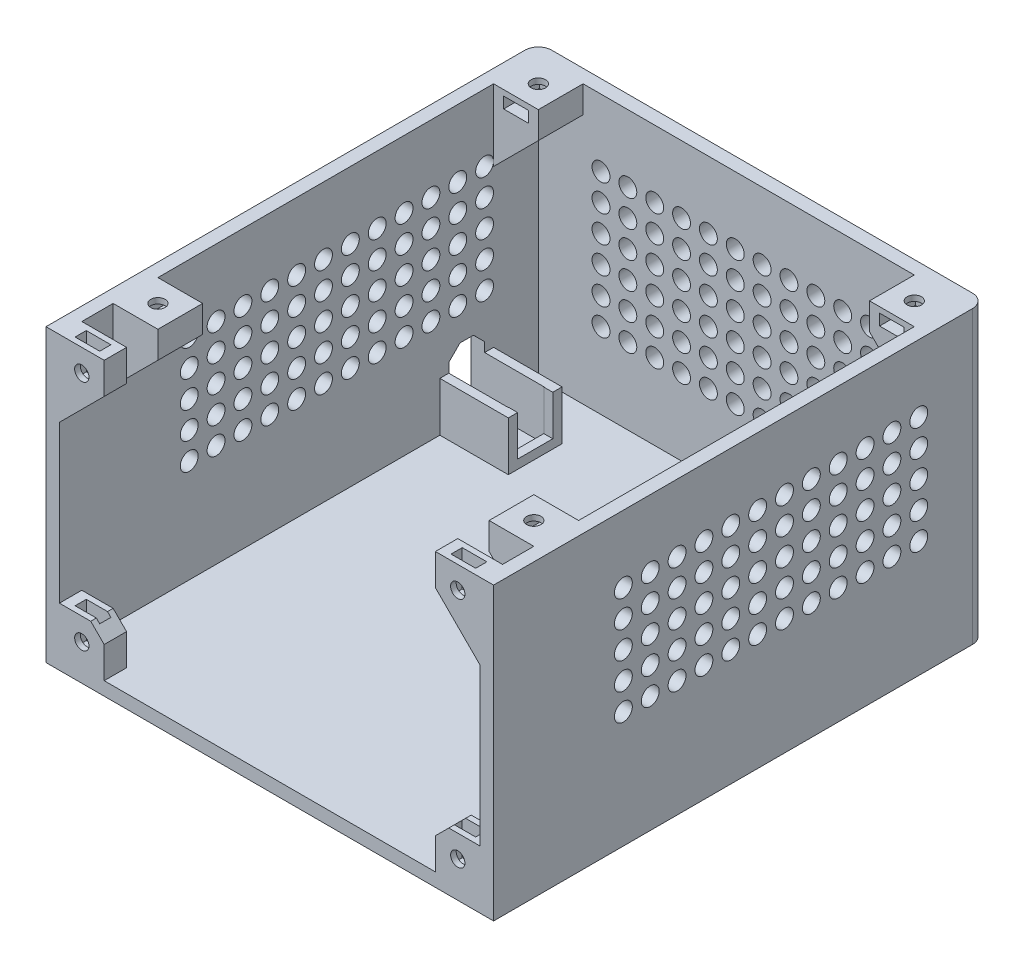
SolidWorks part; units mm, degrees
ref_plane "Спереди" through (0, 0, 0) normal (0, 0, 1) x (1, 0, 0)
ref_plane "Сверху" through (0, 0, 0) normal (0, 1, 0) x (1, 0, 0)
ref_plane "Справа" through (0, 0, 0) normal (1, 0, 0) x (0, 0, -1)
sketch "Эскиз2" plane through (0, 0, 0) normal (0, 0, 1) x (1, 0, 0)
  line L1 (-50, 32.5) -> (50, 32.5)
  line L2 (-50, 32.5) -> (-50, -32.5)
  line L3 (-50, -32.5) -> (50, -32.5)
  line L4 (50, 32.5) -> (50, -32.5)
  line L5 (-50, 32.5) -> (50, -32.5) construction
  line L6 (-50, -32.5) -> (50, 32.5) construction
  point P0 (0, 0)
  dimension "D1" = 65
  dimension "D2" = 100
extrude "Бобышка-Вытянуть1" add sketch "Эскиз2" along normal blind 110
sketch "Эскиз3" plane through (0, 32.5, 0) normal (0, 1, 0) x (1, 0, 0)
  line L0 (-50, -110) -> (-50, 0) construction
  line L1 (-47, -3) -> (47, -3)
  line L2 (-47, -3) -> (-47, -110)
  line L3 (-47, -110) -> (47, -110)
  line L4 (47, -3) -> (47, -110)
  line L5 (-47, -3) -> (47, -110) construction
  line L6 (-47, -110) -> (47, -3) construction
  line L8 (50, 0) -> (-50, 0) construction
  point P0 (0, -56.5)
  dimension "D1" = 107
  dimension "D2" = 94
  dimension "D3" = 3
  dimension "D4" = 3
extrude "Вырез-Вытянуть1" cut sketch "Эскиз3" against normal blind 62
sketch "Эскиз4" plane through (0, 0, 110) normal (0, 0, 1) x (1, 0, 0)
  line L1 (-47, -19.5) -> (-37, -19.5)
  line L2 (-47, -19.5) -> (-47, -29.5)
  line L3 (-47, -29.5) -> (-37, -29.5)
  line L4 (-37, -19.5) -> (-37, -29.5)
  line L5 (-47, -19.5) -> (-37, -29.5) construction
  line L6 (-47, -29.5) -> (-37, -19.5) construction
  line L11 (37, -19.5) -> (47, -19.5)
  line L12 (47, -19.5) -> (47, -29.5)
  line L13 (37, -29.5) -> (47, -29.5)
  line L14 (37, -19.5) -> (37, -29.5)
  circle A0 centre (-42, -24.5) radius 1.6
  circle A2 centre (42, -24.5) radius 1.6
  point P0 (-42, -24.5)
  dimension "D2" = 3.2
  dimension "D1" = 10
  dimension "D3" = 2
extrude "Бобышка-Вытянуть2" add sketch "Эскиз4" against normal blind 5
sketch "Эскиз5" plane through (0, 0, 110) normal (0, 0, 1) x (1, 0, 0)
  line L1 (-47, 32.5) -> (-37, 32.5)
  line L2 (-47, 32.5) -> (-47, 22.5)
  line L3 (-47, 22.5) -> (-37, 22.5)
  line L4 (-37, 32.5) -> (-37, 22.5)
  line L5 (-47, 32.5) -> (-37, 22.5) construction
  line L6 (-47, 22.5) -> (-37, 32.5) construction
  line L10 (37, 32.5) -> (47, 32.5)
  line L12 (37, 32.5) -> (37, 22.5)
  line L13 (37, 22.5) -> (47, 22.5)
  line L14 (47, 32.5) -> (47, 22.5)
  circle A0 centre (-42, 27.5) radius 1.6
  circle A2 centre (42, 27.5) radius 1.6
  point P0 (-42, 27.5)
  dimension "D4" = 3.2
  dimension "D1" = 10
  dimension "D2" = 10
  dimension "D3" = 2
extrude "Бобышка-Вытянуть3" add sketch "Эскиз5" against normal blind 5
sketch "Эскиз6" plane through (0, 32.5, 0) normal (0, 1, 0) x (1, 0, 0)
  line L0 (-37, -105) -> (-37, -110) construction
  line L1 (-44.75, -106.25) -> (-39.25, -106.25)
  line L2 (-44.75, -106.25) -> (-44.75, -108.75)
  line L3 (-44.75, -108.75) -> (-39.25, -108.75)
  line L4 (-39.25, -106.25) -> (-39.25, -108.75)
  line L5 (-44.75, -106.25) -> (-39.25, -108.75) construction
  line L6 (-44.75, -108.75) -> (-39.25, -106.25) construction
  line L11 (39.25, -106.25) -> (39.25, -108.75)
  line L12 (39.25, -106.25) -> (44.75, -106.25)
  line L13 (44.75, -106.25) -> (44.75, -108.75)
  line L14 (39.25, -108.75) -> (44.75, -108.75)
  point P0 (-42, -107.5)
  dimension "D1" = 2.5
  dimension "D2" = 5.5
  dimension "D3" = 5
  dimension "D4" = 2.5
  dimension "D6" = 1.25
  dimension "D7" = 2.25
  dimension "D5" = 2
extrude "Вырез-Вытянуть2" cut sketch "Эскиз6" against normal blind 8
sketch "Эскиз8" plane through (0, -19.5, 0) normal (0, 1, 0) x (1, 0, 0)
  line L1 (-44.75, -106.25) -> (-39.25, -106.25)
  line L2 (-44.75, -106.25) -> (-44.75, -108.75)
  line L3 (-44.75, -108.75) -> (-39.25, -108.75)
  line L4 (-39.25, -106.25) -> (-39.25, -108.75)
  line L5 (-44.75, -106.25) -> (-39.25, -108.75) construction
  line L6 (-44.75, -108.75) -> (-39.25, -106.25) construction
  line L12 (39.25, -106.25) -> (39.25, -108.75)
  line L13 (39.25, -106.25) -> (44.75, -106.25)
  line L14 (39.25, -108.75) -> (44.75, -108.75)
  line L15 (44.75, -106.25) -> (44.75, -108.75)
  point P0 (-42, -107.5)
  dimension "D1" = 2.5
  dimension "D2" = 5.5
  dimension "D3" = 2.5
  dimension "D4" = 5
  dimension "D5" = 2
extrude "Вырез-Вытянуть3" cut sketch "Эскиз8" against normal blind 8
chamfer "Фаска1" distance 3 angle 45 4 edges at (-37, 22.5, 107.5) (-37, -19.5, 107.5) (37, -19.5, 107.5) (37, 22.5, 107.5)
sketch "Эскиз13" plane through (-50, 0, 0) normal (-1, 0, 0) x (0, 0, 1)
  line L0 (15, -29.5) -> (23, -29.5)
  line L1 (23, -29.5) -> (23, -16.4)
  line L2 (23, -16.4) -> (20.5058, -13.9)
  line L3 (20.5058, -13.9) -> (17.4942, -13.9)
  line L4 (17.4942, -13.9) -> (15, -16.4)
  line L5 (15, -16.4) -> (15, -29.5)
  line L6 (0, 32.5) -> (0, -32.5) construction
  line L7 (110, -32.5) -> (0, -32.5) construction
  point P6 (19, -13.9)
  point P7 (19, -29.5)
  dimension "D1" = 8
  dimension "D2" = 15.6
  dimension "D3" = 2.5
  dimension "D4" = 15
  dimension "D5" = 3
extrude "Вырез-Вытянуть5" cut sketch "Эскиз13" against normal up to next
sketch "Эскиз15" plane through (0, -29.5, 0) normal (0, 1, 0) x (1, 0, 0)
  line L0 (-47, -25) -> (-31.7, -25)
  line L1 (-31.7, -25) -> (-31.7, -13)
  line L2 (-31.7, -13) -> (-47, -13)
  line L3 (-47, -13) -> (-47, -15)
  line L4 (-47, -15) -> (-33.7, -15)
  line L5 (-33.7, -15) -> (-33.7, -23)
  line L6 (-33.7, -23) -> (-47, -23)
  line L7 (-47, -25) -> (-47, -23)
  line L9 (-47, -3) -> (-47, -15) construction
  line L11 (47, -3) -> (-47, -3) construction
  dimension "D1" = 8
  dimension "D2" = 2
  dimension "D3" = 2
  dimension "D4" = 2
  dimension "D5" = 15.3
  dimension "D6" = 10
extrude "Бобышка-Вытянуть5" add sketch "Эскиз15" along normal blind 11
sketch "Эскиз16" plane through (0, -18.5, 0) normal (0, 1, 0) x (1, 0, 0)
  line L0 (-31.7, -25) -> (-31.7, -13) construction
  line L2 (-34.6087, -15.0713) -> (-28.7913, -15.0713)
  line L3 (-34.6087, -15.0713) -> (-34.6087, -22.9287)
  line L4 (-34.6087, -22.9287) -> (-28.7913, -22.9287)
  line L5 (-28.7913, -15.0713) -> (-28.7913, -22.9287)
  line L6 (-34.6087, -15.0713) -> (-28.7913, -22.9287) construction
  line L7 (-34.6087, -22.9287) -> (-28.7913, -15.0713) construction
  point P3 (-31.7, -19)
  dimension "D1" = 7.8574
  dimension "D2" = 5.8174
extrude "Вырез-Вытянуть6" cut sketch "Эскиз16" against normal blind 9
sketch "Эскиз31" plane through (0, 0, 3) normal (0, 0, 1) x (1, 0, 0)
  line L0 (47, 32.5) -> (47, 26.5)
  line L1 (-47, 32.5) -> (-37, 32.5)
  line L2 (-47, 32.5) -> (-47, 26.5)
  line L3 (-47, 26.5) -> (-37, 26.5)
  line L4 (-37, 32.5) -> (-37, 26.5)
  line L5 (37, 32.5) -> (47, 32.5)
  line L6 (37, 32.5) -> (37, 26.5)
  line L7 (37, 26.5) -> (47, 26.5)
  dimension "D1" = 10
  dimension "D2" = 6
  dimension "D3" = 2
extrude "Бобышка-Вытянуть10" add sketch "Эскиз31" along normal blind 10 separate body
sketch "Эскиз40" plane through (0, 0, 13) normal (0, 0, 1) x (1, 0, 0)
  line L0 (37, 26.5) -> (47, 26.5)
  line L1 (37, 26.5) -> (47, 26.5) construction
  line L2 (47, 26.5) -> (47, 16.5)
  line L3 (47, 16.5) -> (37, 26.5)
  point P5 (44, 26.5)
  point P7 (44, 26.5)
  dimension "D1" = 10
  dimension "D2" = 10
  dimension "D3" = 14.1421
extrude "Бобышка-Вытянуть14" add sketch "Эскиз40" against normal blind 10
sketch "Эскиз42" plane through (0, 0, 13) normal (0, 0, 1) x (1, 0, 0)
  line L0 (-37, 26.5) -> (-47, 26.5)
  line L1 (-47, 26.5) -> (-47, 16.5)
  line L2 (-47, 16.5) -> (-37, 26.5)
  dimension "D1" = 10
  dimension "D2" = 10
  dimension "D3" = 14.1421
extrude "Бобышка-Вытянуть16" add sketch "Эскиз42" against normal blind 10
sketch "Эскиз32" plane through (0, 32.5, 0) normal (0, 1, 0) x (1, 0, 0)
  circle A0 centre (-42, -8) radius 1.6
  circle A1 centre (42, -8) radius 1.6
  point P3 (0, 0)
  point P11 (0, 0)
  dimension "D1" = 3.2
extrude "Вырез-Вытянуть15" cut sketch "Эскиз32" against normal blind 20
sketch "Эскиз34" plane through (0, 0, 110) normal (0, 0, 1) x (1, 0, 0)
  line L0 (-40, 22.5) -> (-47, 15.5)
  line L1 (-47, -19.5) -> (-47, 22.5) construction
  line L2 (-47, 15.5) -> (-47, 22.5)
  line L3 (-47, 22.5) -> (-40, 22.5)
  line L4 (40, 22.5) -> (47, 22.5)
  line L5 (47, 22.5) -> (47, 15.5)
  line L6 (47, -19.5) -> (47, 22.5) construction
  line L7 (47, 15.5) -> (40, 22.5)
  dimension "D1" = 9.8995
  dimension "D2" = 7
  dimension "D3" = 7
  dimension "D4" = 7
  dimension "D5" = 7
  dimension "D6" = 9.8995
extrude "Бобышка-Вытянуть11" add sketch "Эскиз34" against normal blind 5
fillet "Скругление8" radius 3 1 edges at (-50, 0, 0)
fillet "Скругление9" radius 3 1 edges at (50, 0, 0)
sketch "Эскиз35" plane through (0, 0, 13) normal (0, 0, 1) x (1, 0, 0)
  line L0 (-37, 26.5) -> (-37, 32.5) construction
  line L1 (-44.75, 31.25) -> (-39.25, 31.25)
  line L2 (-44.75, 31.25) -> (-44.75, 28.75)
  line L3 (-44.75, 28.75) -> (-39.25, 28.75)
  line L4 (-39.25, 31.25) -> (-39.25, 28.75)
  line L5 (-44.75, 31.25) -> (-39.25, 28.75) construction
  line L6 (-44.75, 28.75) -> (-39.25, 31.25) construction
  line L7 (-37, 32.5) -> (-47, 32.5) construction
  line L8 (39.25, 31.25) -> (44.75, 31.25)
  line L9 (39.25, 31.25) -> (39.25, 28.75)
  line L10 (39.25, 28.75) -> (44.75, 28.75)
  line L11 (44.75, 31.25) -> (44.75, 28.75)
  point P0 (-42, 30)
  dimension "D1" = 5.5
  dimension "D2" = 2.5
  dimension "D3" = 2.25
  dimension "D4" = 5
  dimension "D5" = 1.25
  dimension "D6" = 2
extrude "Вырез-Вытянуть16" cut sketch "Эскиз35" against normal blind 8
sketch "Эскиз36" plane through (-47, 0, 0) normal (1, 0, 0) x (0, 0, -1)
  line L0 (-98, 32.5) -> (-88, 32.5)
  line L1 (-13, 32.5) -> (-105, 32.5) construction
  line L2 (-88, 32.5) -> (-88, 26.5)
  line L3 (-88, 26.5) -> (-98, 26.5)
  line L4 (-98, 26.5) -> (-98, 32.5)
  line L5 (-105, 32.5) -> (-105, 15.5) construction
  point P5 (-98, 29.5)
  dimension "D1" = 10
  dimension "D2" = 6
  dimension "D3" = 7
extrude "Бобышка-Вытянуть12" add sketch "Эскиз36" along normal blind 10
sketch "Эскиз37" plane through (47, 0, 0) normal (-1, 0, 0) x (0, 0, 1)
  line L0 (98, 32.5) -> (88, 32.5)
  line L1 (105, 32.5) -> (13, 32.5) construction
  line L2 (88, 32.5) -> (88, 26.5)
  line L3 (88, 26.5) -> (98, 26.5)
  line L4 (98, 26.5) -> (98, 32.5)
  line L5 (105, 15.5) -> (105, 32.5) construction
  dimension "D1" = 10
  dimension "D2" = 6
  dimension "D3" = 6
  dimension "D4" = 7
extrude "Бобышка-Вытянуть13" add sketch "Эскиз37" along normal blind 10
sketch "Эскиз41" plane through (0, 0, 88) normal (0, 0, -1) x (-1, 0, 0)
  line L0 (-47, 26.5) -> (-37, 26.5)
  line L1 (-37, 26.5) -> (-47, 16.5)
  line L2 (-47, 16.5) -> (-47, 26.5)
  dimension "D1" = 10
  dimension "D2" = 10
  dimension "D3" = 14.1421
extrude "Бобышка-Вытянуть15" add sketch "Эскиз41" against normal blind 10
sketch "Эскиз43" plane through (0, 0, 88) normal (0, 0, -1) x (-1, 0, 0)
  line L0 (37, 26.5) -> (47, 26.5)
  line L1 (47, 26.5) -> (47, 16.5)
  line L2 (47, 16.5) -> (37, 26.5)
  dimension "D1" = 10
  dimension "D2" = 14.1421
  dimension "D3" = 10
extrude "Бобышка-Вытянуть17" add sketch "Эскиз43" against normal blind 10
sketch "Эскиз38" plane through (0, 32.5, 0) normal (0, 1, 0) x (1, 0, 0)
  circle A0 centre (-42, -93) radius 1.6
  circle A1 centre (42, -93) radius 1.6
  dimension "D1" = 3.2
  dimension "D2" = 2
extrude "Вырез-Вытянуть17" cut sketch "Эскиз38" against normal blind 20
sketch "Эскиз39" plane through (0, 0, 88) normal (0, 0, -1) x (-1, 0, 0)
  line L0 (-37, 32.5) -> (-47, 32.5) construction
  line L1 (-44.75, 31.25) -> (-39.25, 31.25)
  line L2 (-44.75, 31.25) -> (-44.75, 28.75)
  line L3 (-44.75, 28.75) -> (-39.25, 28.75)
  line L4 (-39.25, 31.25) -> (-39.25, 28.75)
  line L5 (-44.75, 31.25) -> (-39.25, 28.75) construction
  line L6 (-44.75, 28.75) -> (-39.25, 31.25) construction
  line L7 (-37, 32.5) -> (-37, 26.5) construction
  line L8 (39.25, 31.25) -> (44.75, 31.25)
  line L9 (39.25, 31.25) -> (39.25, 28.75)
  line L10 (39.25, 28.75) -> (44.75, 28.75)
  line L11 (44.75, 31.25) -> (44.75, 28.75)
  point P0 (-42, 30)
  dimension "D1" = 2.5
  dimension "D2" = 5.5
  dimension "D3" = 1.25
  dimension "D4" = 2.25
  dimension "D5" = 5
  dimension "D6" = 2
extrude "Вырез-Вытянуть18" cut sketch "Эскиз39" against normal blind 8
sketch "Эскиз46" plane through (-50, 0, 0) normal (-1, 0, 0) x (0, 0, 1)
  line L0 (110, 32.5) -> (3, 32.5) construction
  line L1 (0, -32.5) -> (0, 32.5) construction
  circle A0 centre (15, 17.5) radius 2
  circle A1 centre (21, 17.5) radius 2
  circle A2 centre (27, 17.5) radius 2
  circle A3 centre (33, 17.5) radius 2
  circle A4 centre (39, 17.5) radius 2
  circle A5 centre (45, 17.5) radius 2
  circle A6 centre (51, 17.5) radius 2
  circle A7 centre (57, 17.5) radius 2
  circle A8 centre (63, 17.5) radius 2
  circle A9 centre (69, 17.5) radius 2
  circle A10 centre (75, 17.5) radius 2
  circle A11 centre (81, 17.5) radius 2
  circle A12 centre (21, 11.5) radius 2
  circle A13 centre (27, 11.5) radius 2
  circle A14 centre (33, 11.5) radius 2
  circle A15 centre (39, 11.5) radius 2
  circle A16 centre (45, 11.5) radius 2
  circle A17 centre (51, 11.5) radius 2
  circle A18 centre (57, 11.5) radius 2
  circle A19 centre (63, 11.5) radius 2
  circle A20 centre (69, 11.5) radius 2
  circle A21 centre (75, 11.5) radius 2
  circle A22 centre (81, 11.5) radius 2
  circle A23 centre (15, 11.5) radius 2
  circle A24 centre (15, 5.5) radius 2
  circle A25 centre (21, 5.5) radius 2
  circle A26 centre (27, 5.5) radius 2
  circle A27 centre (33, 5.5) radius 2
  circle A28 centre (39, 5.5) radius 2
  circle A29 centre (45, 5.5) radius 2
  circle A30 centre (51, 5.5) radius 2
  circle A31 centre (57, 5.5) radius 2
  circle A32 centre (63, 5.5) radius 2
  circle A33 centre (69, 5.5) radius 2
  circle A34 centre (75, 5.5) radius 2
  circle A35 centre (81, 5.5) radius 2
  circle A36 centre (15, -0.5) radius 2
  circle A37 centre (21, -0.5) radius 2
  circle A38 centre (27, -0.5) radius 2
  circle A39 centre (33, -0.5) radius 2
  circle A40 centre (39, -0.5) radius 2
  circle A41 centre (45, -0.5) radius 2
  circle A42 centre (51, -0.5) radius 2
  circle A43 centre (57, -0.5) radius 2
  circle A44 centre (63, -0.5) radius 2
  circle A45 centre (69, -0.5) radius 2
  circle A46 centre (75, -0.5) radius 2
  circle A47 centre (81, -0.5) radius 2
  circle A48 centre (15, -6.5) radius 2
  circle A49 centre (21, -6.5) radius 2
  circle A50 centre (27, -6.5) radius 2
  circle A51 centre (33, -6.5) radius 2
  circle A52 centre (39, -6.5) radius 2
  circle A53 centre (45, -6.5) radius 2
  circle A54 centre (51, -6.5) radius 2
  circle A55 centre (57, -6.5) radius 2
  circle A56 centre (63, -6.5) radius 2
  circle A57 centre (69, -6.5) radius 2
  circle A58 centre (75, -6.5) radius 2
  circle A59 centre (81, -6.5) radius 2
  dimension "D1" = 4
  dimension "D2" = 15
  dimension "D3" = 15
  dimension "D4" = 12
  dimension "D5" = 5
extrude "Вырез-Вытянуть31" cut sketch "Эскиз46" against normal blind 100
sketch "Эскиз47" plane through (0, 0, 0) normal (0, 0, -1) x (-1, 0, 0)
  line L0 (-47, 32.5) -> (47, 32.5) construction
  line L1 (-50, -32.5) -> (-50, 32.5) construction
  line L2 (50, 32.5) -> (50, -32.5) construction
  circle A0 centre (-33, 17.5) radius 2
  circle A1 centre (-27, 17.5) radius 2
  circle A2 centre (-21, 17.5) radius 2
  circle A3 centre (-15, 17.5) radius 2
  circle A4 centre (-9, 17.5) radius 2
  circle A5 centre (-3, 17.5) radius 2
  circle A6 centre (3, 17.5) radius 2
  circle A7 centre (9, 17.5) radius 2
  circle A8 centre (15, 17.5) radius 2
  circle A9 centre (21, 17.5) radius 2
  circle A10 centre (27, 17.5) radius 2
  circle A11 centre (33, 17.5) radius 2
  circle A12 centre (-27, 11.5) radius 2
  circle A13 centre (-21, 11.5) radius 2
  circle A14 centre (-15, 11.5) radius 2
  circle A15 centre (-9, 11.5) radius 2
  circle A16 centre (-3, 11.5) radius 2
  circle A17 centre (3, 11.5) radius 2
  circle A18 centre (9, 11.5) radius 2
  circle A19 centre (15, 11.5) radius 2
  circle A20 centre (21, 11.5) radius 2
  circle A21 centre (27, 11.5) radius 2
  circle A22 centre (33, 11.5) radius 2
  circle A23 centre (-27, 5.5) radius 2
  circle A24 centre (-21, 5.5) radius 2
  circle A25 centre (-15, 5.5) radius 2
  circle A26 centre (-9, 5.5) radius 2
  circle A27 centre (-3, 5.5) radius 2
  circle A28 centre (3, 5.5) radius 2
  circle A29 centre (9, 5.5) radius 2
  circle A30 centre (15, 5.5) radius 2
  circle A31 centre (21, 5.5) radius 2
  circle A32 centre (27, 5.5) radius 2
  circle A33 centre (33, 5.5) radius 2
  circle A34 centre (-27, -0.5) radius 2
  circle A35 centre (-21, -0.5) radius 2
  circle A36 centre (-15, -0.5) radius 2
  circle A37 centre (-9, -0.5) radius 2
  circle A38 centre (-3, -0.5) radius 2
  circle A39 centre (3, -0.5) radius 2
  circle A40 centre (9, -0.5) radius 2
  circle A41 centre (15, -0.5) radius 2
  circle A42 centre (21, -0.5) radius 2
  circle A43 centre (27, -0.5) radius 2
  circle A44 centre (33, -0.5) radius 2
  circle A45 centre (-27, -6.5) radius 2
  circle A46 centre (-21, -6.5) radius 2
  circle A47 centre (-15, -6.5) radius 2
  circle A48 centre (-9, -6.5) radius 2
  circle A49 centre (-3, -6.5) radius 2
  circle A50 centre (3, -6.5) radius 2
  circle A51 centre (9, -6.5) radius 2
  circle A52 centre (15, -6.5) radius 2
  circle A53 centre (21, -6.5) radius 2
  circle A54 centre (27, -6.5) radius 2
  circle A55 centre (33, -6.5) radius 2
  circle A56 centre (-27, -12.5) radius 2
  circle A57 centre (-21, -12.5) radius 2
  circle A58 centre (-15, -12.5) radius 2
  circle A59 centre (-9, -12.5) radius 2
  circle A60 centre (-3, -12.5) radius 2
  circle A61 centre (3, -12.5) radius 2
  circle A62 centre (9, -12.5) radius 2
  circle A63 centre (15, -12.5) radius 2
  circle A64 centre (21, -12.5) radius 2
  circle A65 centre (27, -12.5) radius 2
  circle A66 centre (33, -12.5) radius 2
  circle A67 centre (-33, 11.5) radius 2
  circle A68 centre (-33, 5.5) radius 2
  circle A69 centre (-33, -0.5) radius 2
  circle A70 centre (-33, -6.5) radius 2
  circle A71 centre (-33, -12.5) radius 2
  dimension "D1" = 4
  dimension "D2" = 15
  dimension "D3" = 17
  dimension "D6" = 17
  dimension "D4" = 12
  dimension "D5" = 6
extrude "Вырез-Вытянуть32" cut sketch "Эскиз47" against normal blind 6
